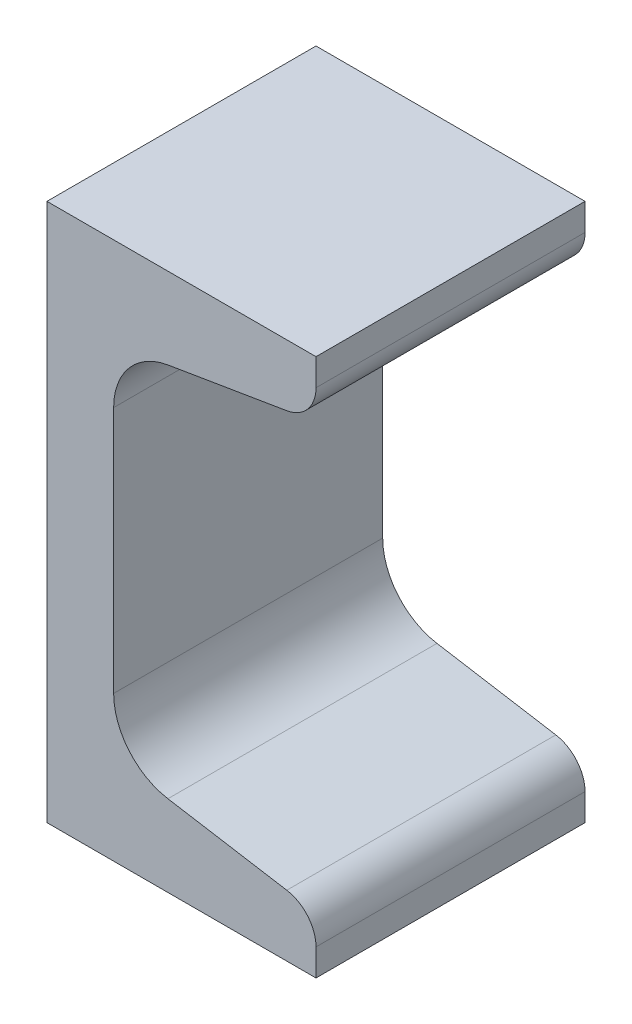
SolidWorks part; units mm, degrees
ref_plane "Plane1" through (0, 0, 0) normal (0, 0, 1) x (1, 0, 0)
ref_plane "Plane2" through (0, 0, 0) normal (0, 1, 0) x (-1, 0, 0)
ref_plane "Plane3" through (0, 0, 0) normal (1, 0, 0) x (0, 0, -1)
sketch "Sketch1" plane through (0, 0, 0) normal (0, 0, 1) x (1, 0, 0)
  line L0 (0, 0) -> (0, 50.8)
  line L1 (0, 50.8) -> (25.4, 50.8)
  line L2 (0, 0) -> (25.4, 0)
  line L3 (7.8492, 0) -> (-7.8492, 0) construction
  line L4 (0, -15.6984) -> (0, 15.6984) construction
  line L12 (6.2965, 37.0849) -> (6.2965, 13.7151)
  line L15 (25.4, 50.8) -> (25.4, 48.26)
  line L16 (25.4, 0) -> (25.4, 2.54)
  line L17 (11.4196, 43.1326) -> (22.6409, 45.0029)
  line L18 (11.4196, 7.6674) -> (22.6409, 5.7971)
  arc A9 (6.2965, 13.7151) -> (11.4196, 7.6674) centre (12.4276, 13.7151) ccw
  arc A10 (6.2965, 37.0849) -> (11.4196, 43.1326) centre (12.4276, 37.0849) cw
  arc A11 (25.4, 48.26) -> (22.6409, 45.0029) centre (22.098, 48.26) cw
  arc A12 (25.4, 2.54) -> (22.6409, 5.7971) centre (22.098, 2.54) ccw
  dimension "RI" = 6.1311
  dimension "D2" = 9.463
  dimension "RA" = 3.302
  dimension "DEPTH" = 50.8
  dimension "BF" = 25.4
  dimension "TW" = 6.2965
  dimension "d1" = 23.3698
extrude "BaseAlumChannel" add sketch "Sketch1" along normal mid plane 25.4
